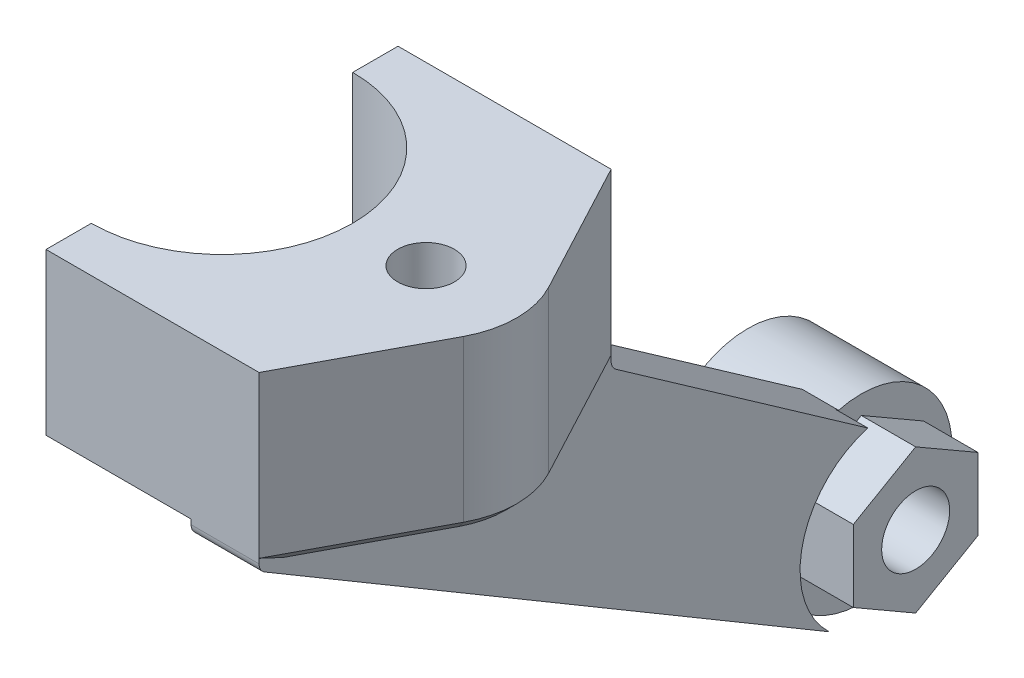
SolidWorks part; units mm, degrees
ref_plane "Front Plane" through (0, 0, 0) normal (0, 0, 1) x (1, 0, 0)
ref_plane "Top Plane" through (0, 0, 0) normal (0, 1, 0) x (1, 0, 0)
ref_plane "Right Plane" through (0, 0, 0) normal (1, 0, 0) x (0, 0, -1)
sketch "Sketch1" plane through (0, 0, 0) normal (0, 1, 0) x (1, 0, 0)
  line L0 (-9.4, 13.1461) -> (-9.4, -15.9532) construction
  line L1 (-19.9267, 0) -> (20.4407, 0) construction
  line L2 (-8.1986, 15.9137) -> (-8.1986, -9.3901) construction
  line L3 (0, -5.765) -> (-8.1986, -5.765) construction
  line L4 (-8.1986, -5.765) -> (-10.7657, -0.9393) construction
  line L5 (0, 5.765) -> (-8.1986, 5.765) construction
  line L6 (-8.1986, 5.765) -> (-10.7657, 0.9393) construction
  line L7 (0, 7.765) -> (-9.4, 7.765)
  line L8 (-9.4, 7.765) -> (-12.5314, 1.8786)
  line L9 (0, -7.765) -> (-9.4, -7.765)
  line L10 (-9.4, -7.765) -> (-12.5314, -1.8786)
  line L11 (0, 7.765) -> (0, 5.765)
  line L12 (0, -7.765) -> (0, -5.765)
  circle A0 centre (0, 0) radius 5.765 construction
  circle A1 centre (-9, 0) radius 1.25
  circle A2 centre (-9, 0) radius 2 construction
  circle A3 centre (-9, 0) radius 4 construction
  arc A4 (-12.5314, 1.8786) -> (-12.5314, -1.8786) centre (-9, 0) ccw
  arc A5 (0, 5.765) -> (0, -5.765) centre (0, 0) ccw
  dimension "D1" = 11.53
  dimension "D4" = 2.5
  dimension "D5" = 4
  dimension "D2" = 9.4
  dimension "D3" = 9
  dimension "D7" = 2
  dimension "D8" = 2
  dimension "D9" = 2
extrude "Bracket" add sketch "Sketch1" along normal blind 7.6
ref_plane "Arm Plane" through (-6.4, 0, 0) normal (1, 0, 0) x (0, 0, -1)
sketch "Sketch2" plane through (-6.4, 0, 0) normal (1, 0, 0) x (0, 0, -1)
  line L1 (-7.765, 0) -> (18.163, -15.3425)
  line L2 (7.765, 0) -> (19.2, -8.027)
  line L5 (-7.765, 0) -> (7.765, 0)
  circle A0 centre (20.2, -11.9) radius 4 construction
  arc A1 (18.163, -15.3425) -> (19.2, -8.027) centre (20.2, -11.9) ccw
  circle A2 centre (20.2, -11.9) radius 1.5
  dimension "D1" = 8
  dimension "D4" = 3
  dimension "D2" = 20.2
  dimension "D3" = 11.9
  dimension "D5" = 1
extrude "Arm" add sketch "Sketch2" against normal blind 1.6
sketch "Sketch3" plane through (0, 0, 0) normal (0, -1, 0) x (1, 0, 0)
  circle A2 centre (-9, 0) radius 1.25
  arc A3 (-8, 0.75) -> (-8, -0.75) centre (-9, 0) ccw construction
extrude "Mount Blind" add sketch "Sketch3" against normal blind 1
sketch "Sketch4" plane through (-8, 0, 0) normal (-1, 0, 0) x (0, 0, 1)
  circle A0 centre (-20.2, -11.9) radius 4
  circle A1 centre (-20.2, -11.9) radius 1.5
  circle A2 centre (-20.2, -11.9) radius 1.5 construction
  arc A3 (-19.2, -8.027) -> (-18.163, -15.3425) centre (-20.2, -11.9) ccw construction
extrude "Effector Mount" add sketch "Sketch4" against normal blind 5
sketch "Sketch5" plane through (-3, 0, 0) normal (1, 0, 0) x (0, 0, -1)
  line L1 (20.2, -8.7246) -> (17.45, -10.3123)
  line L2 (17.45, -10.3123) -> (17.45, -13.4877)
  line L3 (17.45, -13.4877) -> (20.2, -15.0754)
  line L4 (20.2, -15.0754) -> (22.95, -13.4877)
  line L5 (22.95, -13.4877) -> (22.95, -10.3123)
  line L6 (22.95, -10.3123) -> (20.2, -8.7246)
  circle A0 centre (20.2, -11.9) radius 2.75 construction
  dimension "D1" = 5.5
extrude "Mount Trap" cut sketch "Sketch5" against normal blind 2.4
sketch "Sketch6" plane through (-8, 0, 0) normal (-1, 0, 0) x (0, 0, 1)
  line L1 (-17.45, -10.3123) -> (-20.2, -8.7246)
  line L2 (-20.2, -8.7246) -> (-22.95, -10.3123)
  line L3 (-22.95, -10.3123) -> (-22.95, -13.4877)
  line L4 (-22.95, -13.4877) -> (-20.2, -15.0754)
  line L5 (-20.2, -15.0754) -> (-17.45, -13.4877)
  line L6 (-17.45, -13.4877) -> (-17.45, -10.3123)
  circle A0 centre (-20.2, -11.9) radius 2.75 construction
  circle A1 centre (-20.2, -11.9) radius 1.5
  circle A2 centre (-20.2, -11.9) radius 1.5 construction
  dimension "D1" = 5.5
extrude "Mount Adaptor" add sketch "Sketch6" along normal blind 2.4
mirror "Mirror" about plane through (0, 0, 0) normal (1, 0, 0) of "Mount Adaptor", "Mount Trap", "Effector Mount", "Mount Blind", "Arm", "Bracket"
sketch "Sketch7" plane through (0, 7.6, 0) normal (0, 1, 0) x (1, 0, 0)
  line L0 (-9.4, -7.765) -> (9.4, -7.765) construction
  line L1 (-13, 24.2) -> (0, 24.2)
  line L2 (-13, 24.2) -> (-13, -7.765)
  line L3 (-13, -7.765) -> (0, -7.765)
  line L4 (0, 24.2) -> (0, -7.765)
  line L8 (-3, 24.2) -> (-8, 24.2) construction
  arc A0 (-12.5314, 1.8786) -> (-12.5314, -1.8786) centre (-9, 0) ccw construction
extrude "Mirror Delete" cut sketch "Sketch7" against normal through all
sketch "Sketch8" plane through (8, 0, 0) normal (1, 0, 0) x (0, 0, -1)
  line L0 (7.765, 0) -> (19.0934, -7.9522)
  line L1 (19.2, -8.027) -> (7.765, 0) construction
  line L2 (-7.765, 0) -> (17.3884, -14.8841)
  line L3 (-7.765, 0) -> (18.163, -15.3425) construction
  line L7 (19.2, -8.027) -> (7.765, 0)
  line L8 (7.765, 0) -> (-7.765, 0)
  line L9 (-7.765, 0) -> (18.163, -15.3425)
  line L11 (7.765, 0) -> (-7.765, 0)
  circle A0 centre (20.2, -11.9) radius 4.1 construction
  arc A1 (17.3884, -14.8841) -> (19.0934, -7.9522) centre (20.2, -11.9) cw
  arc A3 (18.163, -15.3425) -> (19.2, -8.027) centre (20.2, -11.9) ccw
  dimension "D1" = 8.2
  dimension "D2" = 0
extrude "Arm Support" add sketch "Sketch8" along normal blind 1.4
chamfer "Body Chamfer" distance 0.5 angle 45 5 edges at (3.2, 0, 7.765) (3.2, 0, -7.765) (10.9657, 0, -4.8218) (13, 0, 0) (10.9657, 0, 4.8218)
fillet "Arm Fillet" radius 0.5 2 edges at (7.9, 0, -7.765) (7.9, 0, 7.765)
